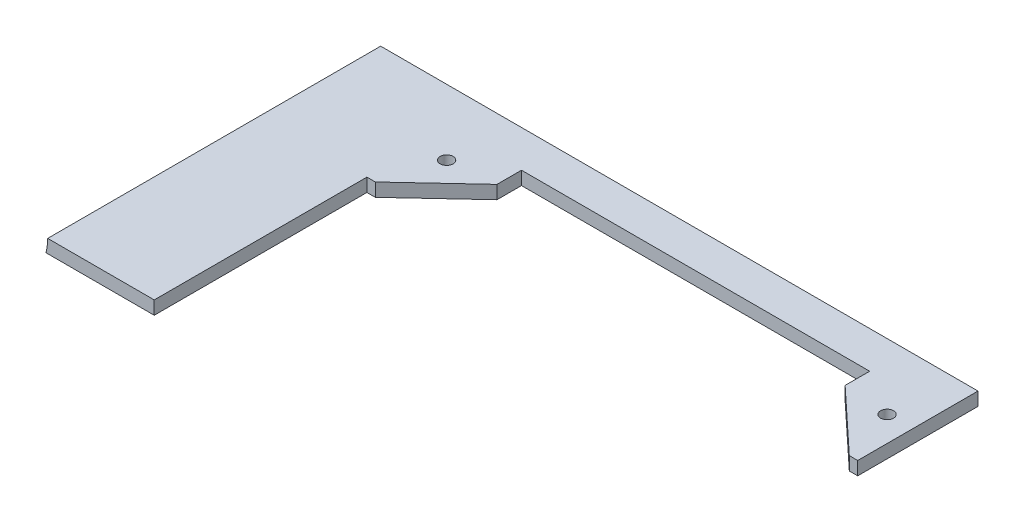
SolidWorks part; units mm, degrees
material "AISI 4130 Steel, annealed at 865C"
ref_plane "X-Y Datum" through (0, 0, 0) normal (0, 0, 1) x (1, 0, 0)
ref_plane "X-Z Datum" through (0, 0, 0) normal (0, 1, 0) x (1, 0, 0)
ref_plane "Y-Z Datum" through (0, 0, 0) normal (1, 0, 0) x (0, 0, -1)
sketch "Sketch1" plane through (0, 0, 0) normal (0, 1, 0) x (1, 0, 0)
  line L1 (-95.25, -38.1) -> (95.25, -38.1)
  line L2 (-95.25, -38.1) -> (-95.25, 38.1)
  line L3 (-95.25, 38.1) -> (95.25, 38.1)
  line L4 (95.25, -38.1) -> (95.25, 38.1)
  line L5 (-95.25, -38.1) -> (95.25, 38.1) construction
  line L6 (-95.25, 38.1) -> (95.25, -38.1) construction
  point P0 (0, 0)
  dimension "D1" = 190.5
  dimension "D2" = 76.2
extrude "Boss-Extrude1" add sketch "Sketch1" along normal blind 3.175 contours L3 L4 L1 L2
sketch "Sketch2" plane through (0, 3.175, 0) normal (0, 1, 0) x (1, 0, 0)
  line L0 (-56.5, 12.6) -> (-41.5, 26.6) construction
  line L1 (-41.5, 26.6) -> (-41.5, 32.45) construction
  line L2 (-41.5, 32.45) -> (41.5, 32.45) construction
  line L3 (41.5, 32.45) -> (41.5, 26.6) construction
  line L4 (-95.25, 38.1) -> (-95.25, -38.1)
  line L5 (-95.25, -38.1) -> (95.25, -38.1)
  line L6 (95.25, -38.1) -> (95.25, 38.1)
  line L7 (95.25, 38.1) -> (-95.25, 38.1)
  line L8 (-95.25, 38.1) -> (-95.25, -38.1)
  line L9 (-95.25, -38.1) -> (95.25, -38.1)
  line L10 (95.25, -38.1) -> (95.25, 38.1)
  line L11 (95.25, 38.1) -> (-95.25, 38.1)
  line L12 (41.5, 26.6) -> (56.5, 12.6) construction
  line L13 (-56.5, 12.6) -> (-41.5, 26.6)
  line L14 (-41.5, 26.6) -> (-41.5, 32.45)
  line L15 (-41.5, 32.45) -> (41.5, 32.45)
  line L16 (41.5, 32.45) -> (41.5, 26.6)
  line L17 (41.5, 26.6) -> (56.5, 12.6)
  line L18 (56.5, 12.6) -> (95.25, 12.6)
  line L19 (-56.5, 12.6) -> (-58.5, 12.6)
  line L20 (58.5, -451.9) -> (58.5, 38.1) construction
  line L21 (58.5, 12.6) -> (58.5, 38.1)
  line L22 (-58.5, 38.1) -> (-58.5, -451.9) construction
  line L23 (-58.5, 38.1) -> (-58.5, -38.1)
  circle A0 centre (-52.5052, 25.6052) radius 1.5453 construction
  circle A1 centre (52.5, 25.6052) radius 1.5453 construction
  circle A2 centre (-52.5052, 25.6052) radius 1.5453
  circle A3 centre (52.5, 25.6052) radius 1.5453
  line M6 (-95.25, -38.1) -> (95.25, -38.1)
  line M7 (95.25, -38.1) -> (95.25, 38.1)
  line M8 (95.25, 38.1) -> (-95.25, 38.1)
  dimension "D1" = 0
extrude "Cut-Extrude4" cut sketch "Sketch2" against normal through all contours L13 L19 L8 L18 L17 L16 L15 L14 M6 M7 | L21 L18 L10 M8 | A2 | A3 | A2 region at (14.8389, 3.175, 6.0761) region at (76.875, 3.175, -25.35) region at (-52.5052, 3.175, -25.6052) region at (52.5, 3.175, -25.6052)
sketch "Sketch3" plane through (0, 0, -38.1) normal (0, 0, -1) x (-1, 0, 0)
  line L4 (95.25, 3.175) -> (-58.5, 3.175)
  line L5 (-58.5, 3.175) -> (-58.5, 0)
  line L6 (-58.5, 0) -> (95.25, 0)
  line L7 (95.25, 0) -> (95.25, 3.175)
  line L8 (95.25, 3.175) -> (-58.5, 3.175)
  line L9 (-58.5, 3.175) -> (-58.5, 0)
  line L10 (-58.5, 0) -> (95.25, 0)
  line L11 (95.25, 0) -> (95.25, 3.175)
  dimension "D1" = 0
extrude "Boss-Extrude2" add sketch "Sketch3" along normal blind 3.175
sketch "Sketch6" plane through (0, 0, 0) normal (0, -1, 0) x (1, 0, 0)
  line L0 (58.5, -41.275) -> (-95.25, -41.275) construction
  line L1 (58.5, -41.275) -> (-95.25, -41.275) construction
  line L14 (58.5, -38.1) -> (-95.25, -38.1) construction
  dimension "D1" = 3.175
sketch "Sketch7" plane through (0, 3.175, 0) normal (0, 1, 0) x (1, 0, 0)
  line L2 (-95.25, 38.1) -> (58.5, 38.1)
  line L3 (-95.25, 38.1) -> (58.5, 38.1) construction
  dimension "D1" = 3.175
sketch3d "3DSketch1"
  line L0 (-96.6, 3.175, 467.8839) -> (-96.6, 3.175, -36.6546)
  line L1 (-96.6, 3.175, -36.6546) -> (-96.6, 3.175, -207.1597)
sweep "Cut-Sweep1" cut path "3DSketch1" circular profile diameter 25.4 parameters "D3"=25.4
